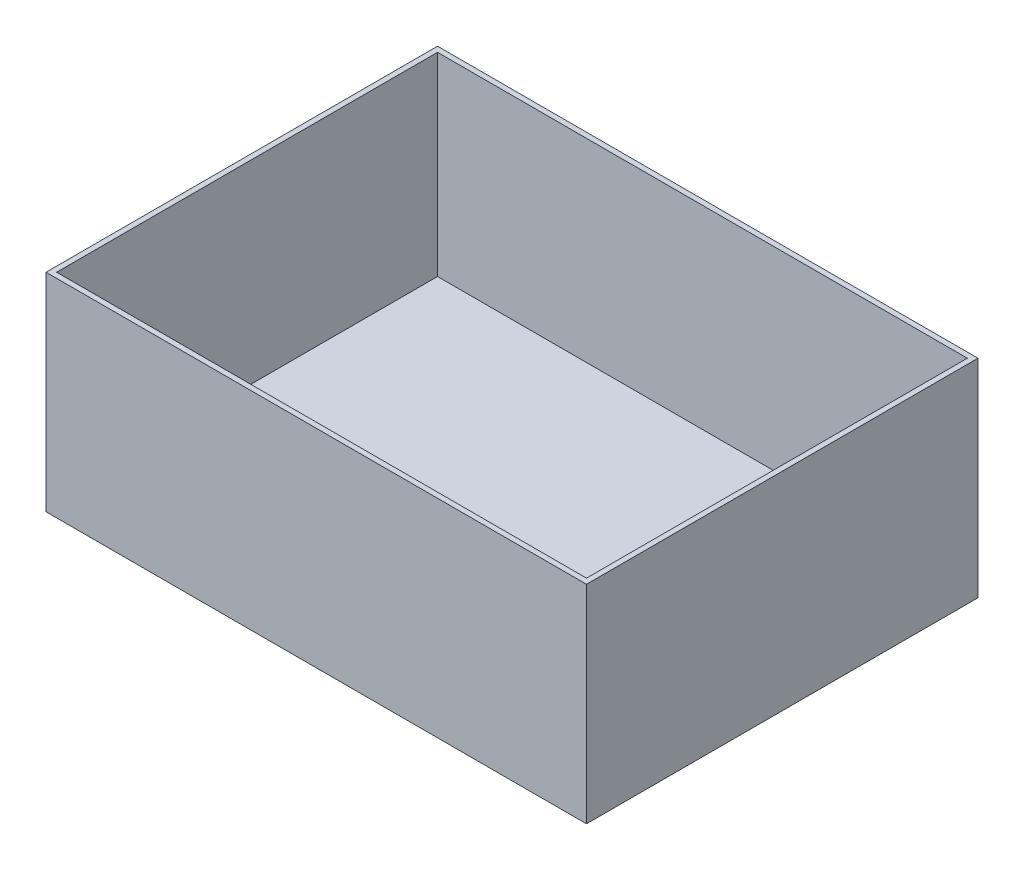
SolidWorks part; units mm, degrees
ref_plane "Front Plane" through (0, 0, 0) normal (0, 0, 1) x (1, 0, 0)
ref_plane "Top Plane" through (0, 0, 0) normal (0, 1, 0) x (1, 0, 0)
ref_plane "Right Plane" through (0, 0, 0) normal (1, 0, 0) x (0, 0, -1)
sketch "Sketch1" plane through (0, 0, 0) normal (0, 1, 0) x (1, 0, 0)
  line L1 (0, 0) -> (645.16, 0)
  line L2 (0, 0) -> (0, 467.36)
  line L3 (0, 467.36) -> (645.16, 467.36)
  line L4 (645.16, 0) -> (645.16, 467.36)
  dimension "D1" = 467.36
  dimension "D2" = 645.16
extrude "Boss-Extrude1" add sketch "Sketch1" along normal blind 241.3
shell "Shell1" thickness 6.35 removed face at (322.58, 241.3, -233.68)
sketch "Sketch2" plane through (0, 241.3, 0) normal (0, 1, 0) x (1, 0, 0)
  line L1 (0, 467.36) -> (645.16, 467.36)
  line L2 (0, 467.36) -> (0, 0)
  line L3 (0, 0) -> (645.16, 0)
  line L4 (645.16, 467.36) -> (645.16, 0)
  line L5 (6.35, 461.01) -> (638.81, 461.01)
  line L6 (6.35, 461.01) -> (6.35, 6.35)
  line L7 (6.35, 6.35) -> (638.81, 6.35)
  line L8 (638.81, 461.01) -> (638.81, 6.35)
extrude "Boss-Extrude2" add sketch "Sketch2" along normal blind 6.35
sketch "Sketch3" plane through (0, 6.35, 0) normal (0, 1, 0) x (1, 0, 0)
  line L1 (6.35, 461.01) -> (638.81, 461.01)
  line L2 (6.35, 461.01) -> (6.35, 6.35)
  line L3 (6.35, 6.35) -> (638.81, 6.35)
  line L4 (638.81, 461.01) -> (638.81, 6.35)
extrude "Boss-Extrude3" add sketch "Sketch3" along normal blind 9.525
